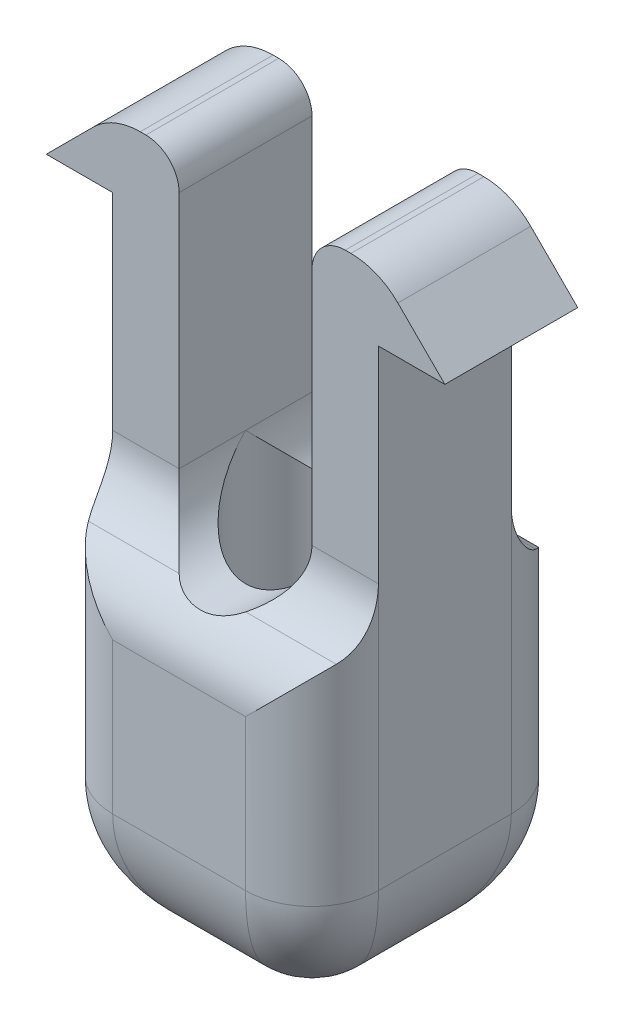
SolidWorks part; units mm, degrees
ref_plane "Front Plane" through (0, 0, 0) normal (0, 0, 1) x (1, 0, 0)
ref_plane "Top Plane" through (0, 0, 0) normal (0, 1, 0) x (1, 0, 0)
ref_plane "Right Plane" through (0, 0, 0) normal (1, 0, 0) x (0, 0, -1)
sketch "Sketch1" plane through (0, 0, 0) normal (0, 1, 0) x (1, 0, 0)
  line L1 (-4, 4) -> (4, 4)
  line L2 (-4, 4) -> (-4, -4)
  line L3 (-4, -4) -> (4, -4)
  line L4 (4, 4) -> (4, -4)
  circle A0 centre (0, 0) radius 2
  point P6 (0, -4)
  point P8 (4, 0)
  dimension "D1" = 4
  dimension "D2" = 8
  dimension "D3" = 8
extrude "Boss-Extrude1" add sketch "Sketch1" along normal blind 10
extrude "Boss-Extrude2" add sketch "Sketch1<2>" along normal blind 3 contours A0 region at (0, 0, 0)
sketch "Sketch1<2>" plane through (0, 0, 0) normal (0, 1, 0) x (1, 0, 0) same geometry as "Sketch1"
sketch "Sketch3" plane through (0, 0, 0) normal (0, 0, 1) x (1, 0, 0)
  line L0 (-4, 18.2) -> (-6, 18.2)
  line L1 (-6, 18.2) -> (-4, 20.2)
  line L2 (-4, 20.2) -> (-2, 20.2)
  line L3 (-2, 20.2) -> (-2, 10)
  line L4 (-2, 10) -> (-4, 10)
  line L5 (-4, 10) -> (-4, 18.2)
  line L6 (0, 0) -> (0, 50000) construction
  line L7 (4, 10) -> (4, 18.2)
  line L8 (2, 10) -> (4, 10)
  line L9 (2, 20.2) -> (2, 10)
  line L10 (4, 20.2) -> (2, 20.2)
  line L11 (6, 18.2) -> (4, 20.2)
  line L12 (4, 18.2) -> (6, 18.2)
  dimension "D1" = 8.2
  dimension "D2" = 2
  dimension "D3" = 2
  dimension "D4" = 2
  dimension "D5" = 2
extrude "Boss-Extrude3" add sketch "Sketch3" along normal blind 2 and the other way blind 2
fillet "Fillet1" radius 4 4 edges at (0, 0, -4) (4, 0, 0) (-4, 0, 0) (0, 0, 4)
fillet "Fillet2" radius 2 4 edges at (2, 10, 1) (-2, 10, 1) (2, 10, -1) (-2, 10, -1)
fillet "Fillet5" radius 2 4 edges at (-2, 10, 2) (2, 10, 2) (-2, 10, -2) (2, 10, -2)
fillet "Fillet6" radius 2 10 edges at (-2, 10, 4) (2, 10, -4) (4, 7, 4) (2.8284, 1.1716, 2.8284) (-2.8284, 1.1716, -2.8284) (-4, 7, 4) (-2.8284, 1.1716, 2.8284) (2.8284, 1.1716, -2.8284) (-4, 7, -4) (4, 7, -4)
fillet "Fillet8" radius 2 2 edges at (-4, 20.2, 0) (4, 20.2, 0)
fillet "Fillet9" radius 1 2 edges at (-2, 20.2, 0) (2, 20.2, 0)
sketch "Sketch4" plane through (0, 0, -4) normal (0, 0, -1) x (-1, 0, 0)
  line L0 (-2, 4) -> (2, 8.5359) construction
  line L1 (-2, 8.5359) -> (2, 4) construction
  circle A0 centre (0, 6.2679) radius 1.5
  point P9 (0, 8.5359)
  point P10 (0, 6.2679)
  point P16 (0, 6.2679)
  dimension "D1" = 3
extrude "Cut-Extrude1" cut sketch "Sketch4" against normal up to next
